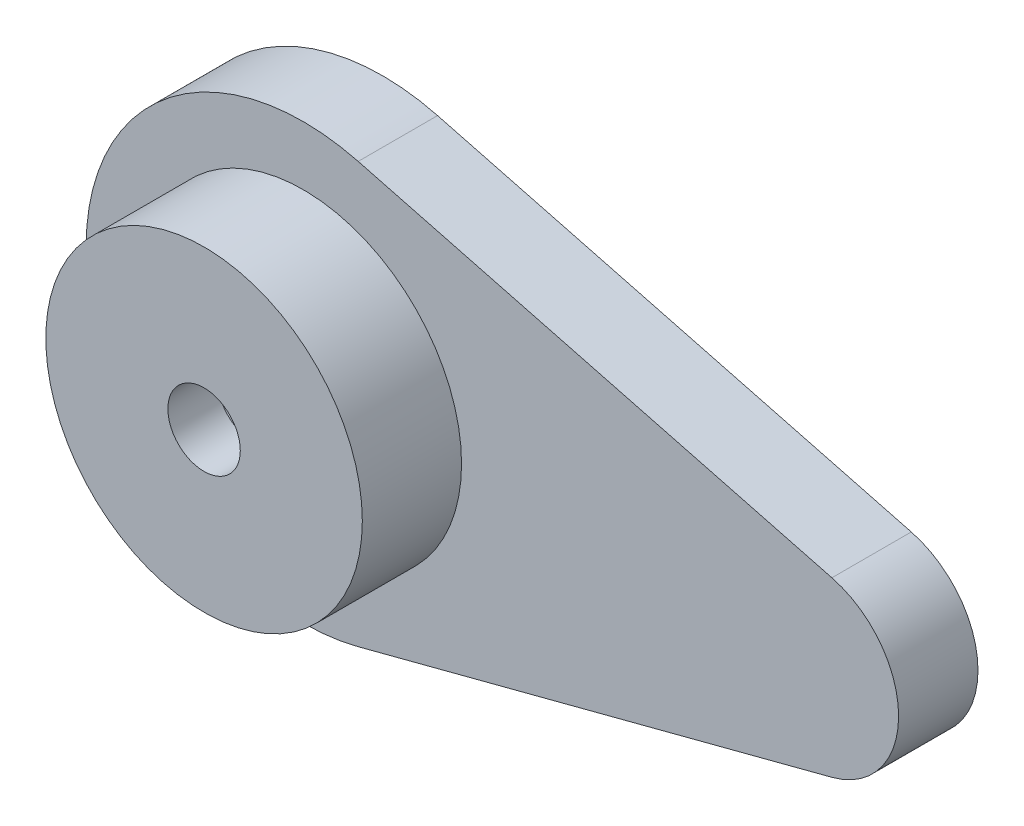
SolidWorks part; units mm, degrees
ref_plane "Front Plane" through (0, 0, 0) normal (0, 0, 1) x (1, 0, 0)
ref_plane "Top Plane" through (0, 0, 0) normal (0, 1, 0) x (1, 0, 0)
ref_plane "Right Plane" through (0, 0, 0) normal (1, 0, 0) x (0, 0, -1)
sketch "Sketch1" plane through (0, 0, 0) normal (0, 0, 1) x (1, 0, 0)
  line L0 (2.7663, 10.5896) -> (26.6374, 4.3539)
  line L3 (2.7663, -10.5896) -> (26.6374, -4.3539)
  arc A2 (2.7663, 10.5896) -> (2.7663, -10.5896) centre (0, 0) ccw
  arc A3 (26.6374, 4.3539) -> (26.6374, -4.3539) centre (25.5, 0) cw
  point P1 (30, 0)
  dimension "D1" = 21.89
  dimension "D3" = 4.5
  dimension "D2" = 30
extrude "Boss-Extrude3" add sketch "Sketch1" along normal blind 5
sketch "Sketch3" plane through (0, 0, 5) normal (0, 0, 1) x (1, 0, 0)
  circle A0 centre (0, 0) radius 7.975
  dimension "D1" = 15.95
extrude "Boss-Extrude4" add sketch "Sketch3" along normal blind 5
sketch "Sketch5" plane through (0, 0, 0) normal (0, 0, -1) x (-1, 0, 0)
  circle A0 centre (0, 0) radius 5.575
  dimension "D1" = 11.15
extrude "Cut-Extrude1" cut sketch "Sketch5" against normal blind 7.5
sketch "Sketch4" plane through (0, 0, 0) normal (0, 0, -1) x (-1, 0, 0)
  line L1 (-1.37, 5.575) -> (1.37, 5.575)
  line L2 (-1.37, 5.575) -> (-1.37, 4.205)
  line L3 (-1.37, 4.205) -> (1.37, 4.205)
  line L4 (1.37, 5.575) -> (1.37, 4.205)
  line L16 (5.575, 1.37) -> (4.205, 1.37)
  line L17 (5.575, 1.37) -> (5.575, -1.37)
  line L18 (5.575, -1.37) -> (4.205, -1.37)
  line L19 (4.205, 1.37) -> (4.205, -1.37)
  line L20 (1.37, -5.575) -> (1.37, -4.205)
  line L21 (1.37, -5.575) -> (-1.37, -5.575)
  line L22 (-1.37, -5.575) -> (-1.37, -4.205)
  line L23 (1.37, -4.205) -> (-1.37, -4.205)
  line L24 (-5.575, -1.37) -> (-4.205, -1.37)
  line L25 (-5.575, -1.37) -> (-5.575, 1.37)
  line L26 (-5.575, 1.37) -> (-4.205, 1.37)
  line L27 (-4.205, -1.37) -> (-4.205, 1.37)
  circle A0 centre (0, 0) radius 5.575 construction
  circle A2 centre (0, 0) radius 5.575 construction
  point P7 (0, 5.575)
  point P23 (0, 0)
  point P26 (0, 0)
  dimension "D2" = 2.74
  dimension "D3" = 1.37
extrude "Boss-Extrude5" add sketch "Sketch4" against normal up to surface (7.5 mm away) up to face at (-5.575, 0, 7.5)
sketch "Sketch6" plane through (0, 0, 10) normal (0, 0, 1) x (1, 0, 0)
  circle A0 centre (0, 0) radius 1.825
  dimension "D1" = 3.65
extrude "Cut-Extrude2" cut sketch "Sketch6" against normal up to surface (2.5 mm away) up to face at (0, 0, 7.5)
sketch "Sketch7" plane through (0, 0, 0) normal (0, 0, -1) x (-1, 0, 0)
  line L0 (-26.6374, 4.3539) -> (-2.7663, 10.5896)
  line L1 (-26.6374, -4.3539) -> (-2.7663, -10.5896)
  arc A0 (-2.7663, -10.5896) -> (-2.7663, 10.5896) centre (0, 0) ccw
  circle A1 centre (0, 0) radius 7.975
  arc A2 (-26.6374, 4.3539) -> (-26.6374, -4.3539) centre (-25.5, 0) ccw
  dimension "D1" = 15.95
  dimension "D2" = 21.89
extrude "Cut-Extrude3" cut sketch "Sketch7" against normal blind 1
fillet "Fillet1" radius 0.5 1 edges at (-7.975, 0, 0)
equation "\"handle_length\"=30.00"
equation "\"key_width\"=2.74"
equation "\"bore_diameter\"=11.15"
equation "\"screw_diameter\"=3.65"
equation "\"handle_width\"=21.89"
equation "\"D1@Sketch1\"=\"handle_width\""
equation "\"extrude_diameter\"=15.95"
equation "\"D1@Sketch3\"=\"extrude_diameter\""
equation "\"D1@Sketch5\"=\"bore_diameter\""
equation "\"D2@Sketch4\"=\"key_width\""
equation "\"D3@Sketch4\"=\"key_length\""
equation "\"D1@Sketch6\"=\"screw_diameter\""
equation "\"D2@Sketch7\"=\"handle_width\""
equation "\"D1@Sketch7\"=\"extrude_diameter\""
equation "\"key_length\"=1.37"
equation "\"D2@Sketch1\"=\"handle_length\""
